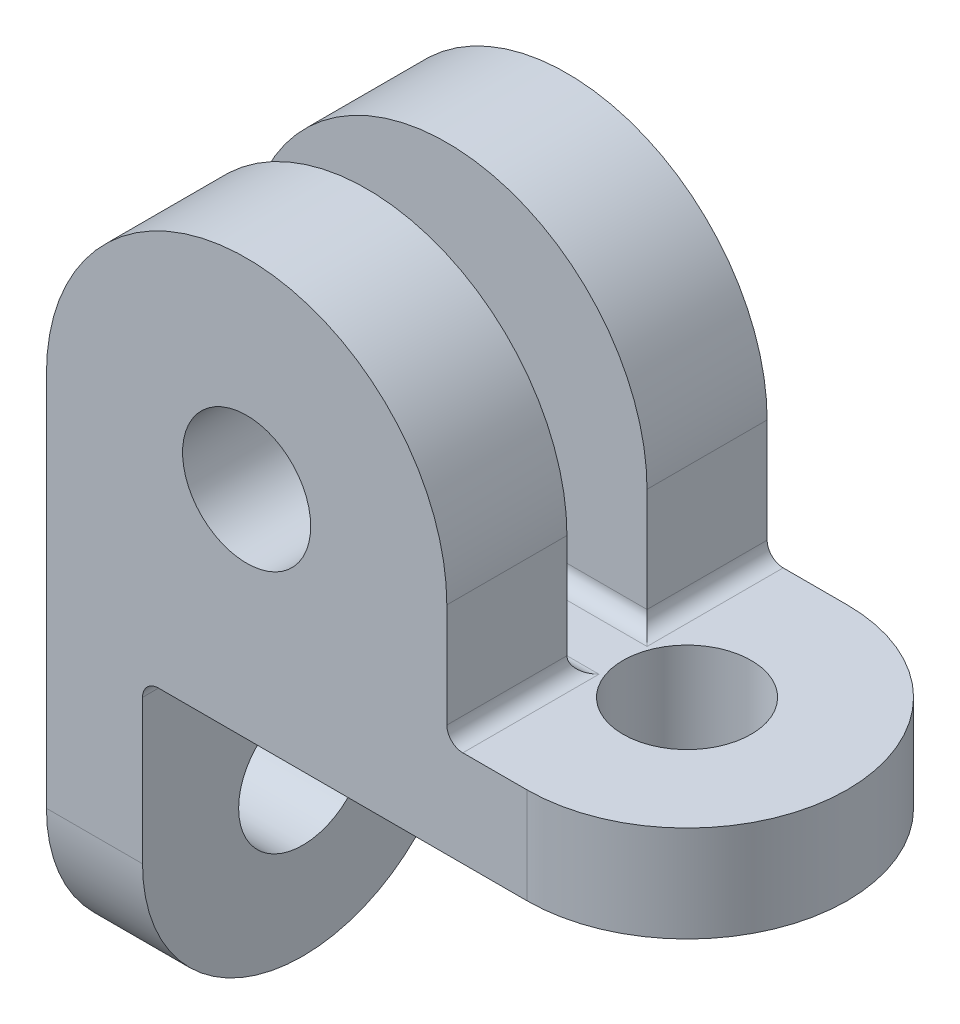
SolidWorks part; units mm, degrees
ref_plane "Front Plane" through (0, 0, 0) normal (0, 0, 1) x (1, 0, 0)
ref_plane "Top Plane" through (0, 0, 0) normal (0, 1, 0) x (1, 0, 0)
ref_plane "Right Plane" through (0, 0, 0) normal (1, 0, 0) x (0, 0, -1)
sketch "Sketch1" plane through (0, 0, 0) normal (0, 1, 0) x (1, 0, 0)
  line L1 (-40, 20) -> (40, 20)
  line L2 (-40, 20) -> (-40, -20)
  line L3 (-40, -20) -> (40, -20)
  line L4 (40, 20) -> (40, -20)
  line L5 (-40, 20) -> (40, -20) construction
  line L6 (-40, -20) -> (40, 20) construction
  point P0 (0, 0)
  dimension "D1" = 80
  dimension "D2" = 40
extrude "Boss-Extrude1" add sketch "Sketch1" along normal blind 12
fillet "Fillet1" 2 edges at (40, 6, 20) (40, 6, -20) type full round first side face at (0, 6, 20) second side face at (0, 6, -20) middle face at (40, 6, 0)
sketch "Sketch2" plane through (0, 12, 0) normal (0, 1, 0) x (1, 0, 0)
  line L1 (-40, -20) -> (10, -20)
  line L2 (-40, -20) -> (-40, -5)
  line L3 (-40, -5) -> (10, -5)
  line L4 (10, -20) -> (10, -5)
extrude "Boss-Extrude2" add sketch "Sketch2" along normal blind 40
fillet "Fillet3" 2 edges at (-40, 52, 12.5) (10, 52, 12.5) type full round first side face at (-40, 21.3333, 1.6667) second side face at (10, 32, 12.5) middle face at (-15, 52, 12.5)
sketch "Sketch4" plane through (0, 0, 20) normal (0, 0, 1) x (1, 0, 0)
  circle A0 centre (-15, 27) radius 8
  dimension "D1" = 16
extrude "Cut-Extrude2" cut sketch "Sketch4" against normal blind 40
mirror "Mirror7" about plane through (0, 0, 0) normal (0, 0, 1) of "Boss-Extrude2", "Cut-Extrude2", "Fillet3"
sketch "Sketch5" plane through (0, 12, 0) normal (0, 1, 0) x (1, 0, 0)
  circle A0 centre (20, 0) radius 8
  dimension "D1" = 16
extrude "Cut-Extrude4" cut sketch "Sketch5" against normal blind 40
sketch "Sketch7" plane through (0, 0, 0) normal (0, -1, 0) x (-1, 0, 0)
  line L0 (-20, 20) -> (40, 20) construction
  line L1 (40, -20) -> (28, -20)
  line L2 (40, -20) -> (40, 20)
  line L3 (40, 20) -> (28, 20)
  line L4 (28, -20) -> (28, 20)
  dimension "D1" = 12
extrude "Boss-Extrude3" add sketch "Sketch7" along normal blind 40
fillet "Fillet4" 2 edges at (-34, -40, 20) (-34, -40, -20) type full round first side face at (-7, 27, 20) second side face at (-7, 27, -20) middle face at (-34, -40, 0)
sketch "Sketch8" plane through (-40, 0, 0) normal (-1, 0, 0) x (0, 0, 1)
  circle A0 centre (0, -20) radius 8
  dimension "D1" = 16
extrude "Cut-Extrude5" cut sketch "Sketch8" against normal blind 40
fillet "Fillet6" radius 2 1 edges at (10, 12, 12.5) type face fillet first side face at (10, 19.5, 12.5) second side face at (20, 12, 8)
fillet "Fillet7" radius 2 1 edges at (-14, 12, 5) type face fillet first side face at (-7, 27, 5) second side face at (10, 19.5, -12.5) second side face at (20, 12, 8) second side face at (-7, 27, -5)
fillet "Fillet8" radius 2 1 edges at (-15, 12, -5) type face fillet first side face at (-7, 27, -5) second side face at (20, 12, 8)
fillet "Fillet9" radius 2 1 edges at (10, 12, -11.5) type face fillet first side face at (10, 18.3172, -10.6828) second side face at (20, 12, 8)
fillet "Fillet10" radius 2 1 edges at (-28, 0, 0) type face fillet first side face at (-28, -20, 8) second side face at (20, 0, 8)
